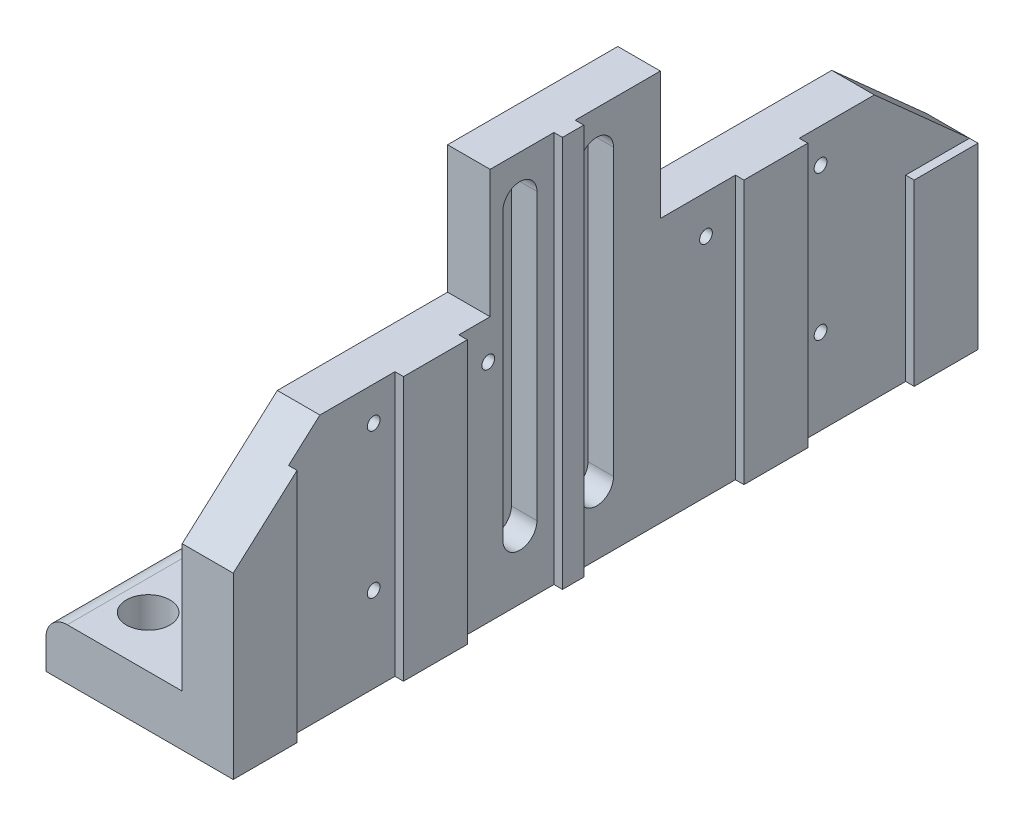
SolidWorks part; units mm, degrees
ref_plane "Front Plane" through (0, 0, 0) normal (0, 0, 1) x (1, 0, 0)
ref_plane "Top Plane" through (0, 0, 0) normal (0, 1, 0) x (1, 0, 0)
ref_plane "Right Plane" through (0, 0, 0) normal (1, 0, 0) x (0, 0, -1)
sketch "Sketch1" plane through (0, 0, 0) normal (0, 1, 0) x (1, 0, 0)
  line L1 (0, 0) -> (4.2, 0)
  line L2 (0, 0) -> (0, 17.5)
  line L3 (0, 17.5) -> (4.2, 17.5)
  line L4 (4.2, 0) -> (4.2, 17.5)
  dimension "D1" = 4.2
  dimension "D2" = 17.5
extrude "Boss-Extrude1" add sketch "Sketch1" along normal blind 1.2
sketch "Sketch2" plane through (0, 1.2, 0) normal (0, 1, 0) x (1, 0, 0)
  line L0 (0, 0) -> (4.2, 0) construction
  line L1 (4.2, 17.5) -> (3.2, 17.5)
  line L2 (4.2, 17.5) -> (4.2, 0)
  line L3 (4.2, 0) -> (3.2, 0)
  line L4 (3.2, 17.5) -> (3.2, 0)
  dimension "D1" = 1
extrude "Boss-Extrude2" add sketch "Sketch2" along normal blind 5
sketch "Sketch3" plane through (4.2, 0, 0) normal (1, 0, 0) x (0, 0, -1)
  line L3 (0, 6.2) -> (17.5, 6.2) construction
  line L9 (0, 4.2) -> (0, 6.2)
  line L10 (0, 6.2) -> (0, 0) construction
  line L11 (0, 6.2) -> (2.2361, 6.2)
  line L12 (2.2361, 6.2) -> (0, 4.2)
  line L13 (17.5, 6.2) -> (15.2639, 6.2)
  line L14 (15.2639, 6.2) -> (17.5, 4.2)
  line L15 (17.5, 6.2) -> (17.5, 0) construction
  line L16 (17.5, 4.2) -> (17.5, 6.2)
  dimension "D1" = 3
  dimension "D2" = 3
  dimension "D3" = 2
extrude "Cut-Extrude1" cut sketch "Sketch3" against normal blind 5 and the other way blind 1.3
sketch "Sketch4" plane through (4.2, 0, 0) normal (1, 0, 0) x (0, 0, -1)
  line L0 (2.2361, 6.2) -> (15.2639, 6.2) construction
  line L1 (6.2361, 6.2) -> (10.2361, 6.2)
  line L2 (6.2361, 6.2) -> (6.2361, 9.2)
  line L3 (6.2361, 9.2) -> (10.2361, 9.2)
  line L4 (10.2361, 6.2) -> (10.2361, 9.2)
  dimension "D1" = 4
  dimension "D2" = 4
  dimension "D3" = 3
extrude "Boss-Extrude3" add sketch "Sketch4" against normal blind 1
sketch "Sketch5" plane through (0, 1.2, 0) normal (0, 1, 0) x (1, 0, 0)
  line L0 (3.2, 17.5) -> (0, 17.5) construction
  line L1 (0, 17.5) -> (0, 0) construction
  line L2 (0, 0) -> (3.2, 0) construction
  circle A0 centre (1.2, 16.3) radius 0.5125
  circle A2 centre (1.2, 1.2) radius 0.5125
  dimension "D1" = 1.2
  dimension "D2" = 1.2
  dimension "D3" = 1.2
  dimension "D4" = 1.2
  dimension "D5" = 1.025
  dimension "D6" = 1.025
extrude "Cut-Extrude2" cut sketch "Sketch5" against normal through all
sketch "Sketch6" plane through (0, 1.2, 0) normal (0, 1, 0) x (1, 0, 0)
  line L0 (3.2, 17.5) -> (0, 17.5) construction
  line L1 (0, 17.5) -> (0, 0) construction
  circle A0 centre (1.4, 8.8) radius 0.5
  dimension "D1" = 8.7
  dimension "D2" = 1.4
extrude "Cut-Extrude3" cut sketch "Sketch6" against normal blind 0.75
sketch "Sketch11" plane through (4.2, 0, 0) normal (1, 0, 0) x (0, 0, -1)
  line L0 (3.5, 0) -> (3.5, 5.4023) construction
  line L2 (0, 0) -> (17.5, 0) construction
  line L5 (3.5, 5.4023) -> (14, 5.4) construction
  line L9 (14, 5.4) -> (14, 0) construction
  circle A0 centre (3.5, 5.4023) radius 0.15
  circle A1 centre (6.1918, 5.3) radius 0.15
  circle A2 centre (3.5, 2) radius 0.15
  circle A3 centre (11.3082, 5.3) radius 0.15
  circle A4 centre (14, 5.4) radius 0.15
  circle A5 centre (14, 2) radius 0.15
  dimension "D1" = 0.3
  dimension "D2" = 0.3
  dimension "D3" = 0.3
  dimension "D4" = 0.3
  dimension "D5" = 0.3
  dimension "D6" = 0.3
  dimension "D7" = 0.1017
extrude "Cut-Extrude5" cut sketch "Sketch11" against normal through all and the other way blind 1.3
sketch "Sketch15" plane through (3.2, 0, 0) normal (-1, 0, 0) x (0, 0, 1)
  line L1 (-14, 5.75) -> (-14.3031, 5.575)
  line L2 (-14.3031, 5.575) -> (-14.3031, 5.225)
  line L3 (-14.3031, 5.225) -> (-14, 5.05)
  line L4 (-14, 5.05) -> (-13.6969, 5.225)
  line L5 (-13.6969, 5.225) -> (-13.6969, 5.575)
  line L6 (-13.6969, 5.575) -> (-14, 5.75)
  line L7 (-11.3082, 5.65) -> (-11.6113, 5.475)
  line L8 (-11.6113, 5.475) -> (-11.6113, 5.125)
  line L9 (-11.6113, 5.125) -> (-11.3082, 4.95)
  line L10 (-11.3082, 4.95) -> (-11.005, 5.125)
  line L11 (-11.005, 5.125) -> (-11.005, 5.475)
  line L12 (-11.005, 5.475) -> (-11.3082, 5.65)
  line L13 (-14, 2.35) -> (-14.3031, 2.175)
  line L14 (-14.3031, 2.175) -> (-14.3031, 1.825)
  line L15 (-14.3031, 1.825) -> (-14, 1.65)
  line L16 (-14, 1.65) -> (-13.6969, 1.825)
  line L17 (-13.6969, 1.825) -> (-13.6969, 2.175)
  line L18 (-13.6969, 2.175) -> (-14, 2.35)
  line L19 (-6.1918, 5.65) -> (-6.495, 5.475)
  line L20 (-6.495, 5.475) -> (-6.495, 5.125)
  line L21 (-6.495, 5.125) -> (-6.1918, 4.95)
  line L22 (-6.1918, 4.95) -> (-5.8887, 5.125)
  line L23 (-5.8887, 5.125) -> (-5.8887, 5.475)
  line L24 (-5.8887, 5.475) -> (-6.1918, 5.65)
  line L25 (-3.5, 5.7523) -> (-3.8031, 5.5773)
  line L26 (-3.8031, 5.5773) -> (-3.8031, 5.2273)
  line L27 (-3.8031, 5.2273) -> (-3.5, 5.0523)
  line L28 (-3.5, 5.0523) -> (-3.1969, 5.2273)
  line L29 (-3.1969, 5.2273) -> (-3.1969, 5.5773)
  line L30 (-3.1969, 5.5773) -> (-3.5, 5.7523)
  line L31 (-3.5, 2.35) -> (-3.8031, 2.175)
  line L32 (-3.8031, 2.175) -> (-3.8031, 1.825)
  line L33 (-3.8031, 1.825) -> (-3.5, 1.65)
  line L34 (-3.5, 1.65) -> (-3.1969, 1.825)
  line L35 (-3.1969, 1.825) -> (-3.1969, 2.175)
  line L36 (-3.1969, 2.175) -> (-3.5, 2.35)
  circle A0 centre (-14, 5.4) radius 0.3031 construction
  circle A1 centre (-11.3082, 5.3) radius 0.3031 construction
  circle A2 centre (-14, 2) radius 0.3031 construction
  circle A3 centre (-6.1918, 5.3) radius 0.3031 construction
  circle A4 centre (-3.5, 5.4023) radius 0.3031 construction
  circle A5 centre (-3.5, 2) radius 0.3031 construction
  dimension "D1" = 0.7
  dimension "D2" = 0.7
  dimension "D3" = 0.7
  dimension "D4" = 0.7
  dimension "D5" = 0.7
  dimension "D6" = 0.7
extrude "Cut-Extrude7" cut sketch "Sketch15" against normal blind 0.2
sketch "Sketch12" plane through (4.2, 0, 0) normal (1, 0, 0) x (0, 0, -1)
  line L0 (8.7361, 8.2) -> (8.7361, 1.5) construction
  line L1 (8.8861, 8.2) -> (8.8861, 1.5)
  line L2 (8.5861, 8.2) -> (8.5861, 1.5)
  line L3 (6.9361, 8.2) -> (6.9361, 1.5) construction
  line L4 (7.0861, 8.2) -> (7.0861, 1.5)
  line L5 (6.7861, 8.2) -> (6.7861, 1.5)
  line L6 (10.2361, 6.2) -> (10.2361, 9.2) construction
  line L7 (0, 0) -> (17.5, 0) construction
  line L8 (10.2361, 9.2) -> (6.2361, 9.2) construction
  arc A0 (8.8861, 8.2) -> (8.5861, 8.2) centre (8.7361, 8.2) ccw
  arc A1 (8.5861, 1.5) -> (8.8861, 1.5) centre (8.7361, 1.5) ccw
  arc A2 (7.0861, 8.2) -> (6.7861, 8.2) centre (6.9361, 8.2) ccw
  arc A3 (6.7861, 1.5) -> (7.0861, 1.5) centre (6.9361, 1.5) ccw
  point P2 (8.7361, 4.85)
  point P7 (6.9361, 4.85)
  dimension "D2" = 0.3
  dimension "D1" = 0.3
  dimension "D3" = 1.5
  dimension "D4" = 1.8
  dimension "D5" = 1.5
  dimension "D6" = 1.5
  dimension "D7" = 1
  dimension "D8" = 1
extrude "Cut-Extrude6" cut sketch "Sketch12" against normal blind 1.3 and the other way blind 1.3
sketch "Sketch14" plane through (4.2, 0, 0) normal (1, 0, 0) x (0, 0, -1)
  line L0 (2.2361, 6.2) -> (6.2361, 6.2) construction
  line L1 (4, 6.2) -> (5.5, 6.2)
  line L2 (4, 6.2) -> (4, 0)
  line L3 (4, 0) -> (5.5, 0)
  line L4 (5.5, 6.2) -> (5.5, 0)
  line L5 (0, 0) -> (17.5, 0) construction
  line L6 (10.2361, 6.2) -> (15.2639, 6.2) construction
  line L7 (0, 4.2) -> (1.5, 4.2)
  line L8 (0, 4.2) -> (0, 0)
  line L9 (0, 0) -> (1.5, 0)
  line L10 (1.5, 4.2) -> (1.5, 0)
  line L11 (12, 6.2) -> (13.5, 6.2)
  line L12 (12, 6.2) -> (12, 0)
  line L13 (12, 0) -> (13.5, 0)
  line L14 (13.5, 6.2) -> (13.5, 0)
  line L15 (10.2361, 9.2) -> (6.2361, 9.2) construction
  line L16 (17.5, 4.2) -> (16, 4.2)
  line L17 (17.5, 4.2) -> (17.5, 0)
  line L18 (17.5, 0) -> (16, 0)
  line L19 (16, 4.2) -> (16, 0)
  line L20 (7.7361, 9.2) -> (8.2361, 9.2)
  line L21 (7.7361, 9.2) -> (7.7361, 0)
  line L22 (7.7361, 0) -> (8.2361, 0)
  line L23 (8.2361, 9.2) -> (8.2361, 0)
  line L24 (8.5861, 8.2) -> (8.5861, 1.5) construction
  line L25 (7.0861, 1.5) -> (7.0861, 8.2) construction
  line L26 (1.5, 4.2) -> (1.5, 5.5416)
  line L27 (0, 4.2) -> (2.2361, 6.2) construction
  line L28 (1.5, 5.5416) -> (0, 4.2)
  line L29 (1.5, 4.2) -> (0, 4.2)
  line L30 (16, 4.2) -> (16, 5.5416)
  line L31 (15.2639, 6.2) -> (17.5, 4.2) construction
  line L32 (16, 5.5416) -> (17.5, 4.2)
  line L33 (16, 4.2) -> (17.5, 4.2)
  line L34 (16, 5.5416) -> (17.5, 4.2)
  dimension "D1" = 1.5
  dimension "D2" = 1.5
  dimension "D3" = 1.5
  dimension "D4" = 2.5
  dimension "D5" = 2.5
  dimension "D6" = 1.5
  dimension "D7" = 0.5
  dimension "D8" = 0.35
  dimension "D9" = 0.65
extrude "Boss-Extrude5" add sketch "Sketch14" along normal blind 0.2 contours L10 L7 L8 L9 | L26 L28 L7 | L4 L1 L2 L3 | L14 L11 L12 L13 | L23 L20 L21 L22 | L16 L19 L18 L17 region at (4.2, 3.1, -4.75) region at (4.2, 4.6472, -1) region at (4.2, 2.1, -0.75) region at (4.2, 3.1, -12.75) region at (4.2, 2.1, -16.75) region at (4.2, 4.6, -7.9861)
fillet "Fillet1" radius 0.5 1 edges at (0, 1.2, -8.75)
sketch "Sketch16" plane through (4.2, 0, 0) normal (1, 0, 0) x (0, 0, -1)
  line L0 (8.7361, 1.5) -> (8.7361, 8.2) construction
  line L1 (8.3361, 1.5) -> (8.3361, 8.2)
  line L2 (9.1361, 1.5) -> (9.1361, 8.2)
  line L3 (6.9361, 1.5) -> (6.9361, 8.2) construction
  line L4 (6.5361, 1.5) -> (6.5361, 8.2)
  line L5 (7.3361, 1.5) -> (7.3361, 8.2)
  arc A0 (8.3361, 1.5) -> (9.1361, 1.5) centre (8.7361, 1.5) ccw
  arc A1 (9.1361, 8.2) -> (8.3361, 8.2) centre (8.7361, 8.2) ccw
  arc A2 (6.5361, 1.5) -> (7.3361, 1.5) centre (6.9361, 1.5) ccw
  arc A3 (7.3361, 8.2) -> (6.5361, 8.2) centre (6.9361, 8.2) ccw
  point P4 (8.7361, 4.85)
  point P9 (6.9361, 4.85)
  dimension "D1" = 0.4
  dimension "D2" = 0.4
extrude "Cut-Extrude8" cut sketch "Sketch16" against normal blind 0.6
